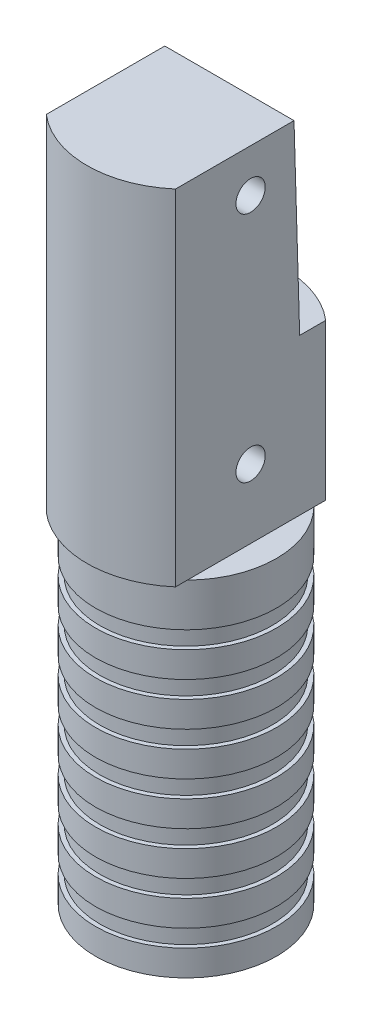
SolidWorks part; units mm, degrees
material "6061-T6 (SS)"
ref_plane "Front Plane" through (0, 0, 0) normal (0, 0, 1) x (1, 0, 0)
ref_plane "Top Plane" through (0, 0, 0) normal (0, 1, 0) x (1, 0, 0)
ref_plane "Right Plane" through (0, 0, 0) normal (1, 0, 0) x (0, 0, -1)
sketch "Sketch2" plane through (0, 0, 0) normal (0, 0, 1) x (1, 0, 0)
  line L0 (-10.5, 0) -> (10.5, 0)
  line L1 (10.5, 0) -> (10.5, -40)
  line L2 (10.5, -40) -> (-1, -40)
  line L4 (0, 0) -> (0, -40)
  line L6 (-10.5, -40) -> (-1, -40)
  line L7 (-10.5, 0) -> (-10.5, -40)
  point P4 (0, 0)
  dimension "D1" = 21
  dimension "D4" = 40
revolve "Revolve1" add sketch "Sketch2" angle 360 about L4 region at (-5.25, -20, 0)
sketch "Sketch3" plane through (0, 0, 0) normal (0, 0, 1) x (1, 0, 0)
  line L0 (-10.5, -40) -> (10.5, -40) construction
  line L1 (-10.5, -40) -> (10.5, -40)
  line L2 (10.5, -40) -> (10.5, -37)
  line L3 (10.5, -40) -> (10.5, 0) construction
  line L4 (10.5, -37) -> (10, -37)
  line L5 (10, -37) -> (10, -35)
  line L6 (10, -35) -> (10.5, -35)
  line L7 (10.5, -37) -> (10.5, -35)
  dimension "D1" = 2
  dimension "D2" = 0.5
  dimension "D3" = 3
revolve "Cut-Revolve1" cut sketch "Sketch3" angle 360 about L4
pattern_linear "LPattern1" count 7 spacing 5 along (0, 1, 0) of "Cut-Revolve1"
sketch "Sketch4" plane through (0, -40, 0) normal (0, -1, 0) x (1, 0, 0)
  point P0 (0, 0)
sketch "Sketch6" plane through (0, 0, 0) normal (0, 1, 0) x (1, 0, 0)
  line L0 (-7.5, 8.7178) -> (-7.5, -8.7178)
  line L2 (0, 0) -> (0, 11.5) construction
  line L3 (7.5, 8.7178) -> (7.5, -8.7178)
  line L4 (0, 0) -> (-7.5, 0) construction
  line L5 (-7.5, 1.5) -> (0, 1.5) construction
  arc A0 (7.5, 8.7178) -> (-7.5, 8.7178) centre (0, 0) ccw
  circle A1 centre (0, 0) radius 10.5 construction
  arc A2 (7.5, -8.7178) -> (-7.5, -8.7178) centre (0, 0) cw
  point P7 (-10.5, 0)
  dimension "D3" = 11.5
  dimension "D1" = 3
  dimension "D2" = 1.5
extrude "Boss-Extrude1" add sketch "Sketch6" along normal blind 40
hole_wizard "Ø15.0 (15) Diameter Hole1" positions "Sketch4" profile "Sketch5" hole size "Ø15.0" standard "ANSI Metric"
sketch "Sketch5" plane through (0, -40, 0) normal (1, 0, 0) x (0, 0, -1)
  line L0 (0, 0) -> (0, 34.5065)
  line L1 (0, 34.5065) -> (7.5, 30)
  line L2 (7.5, 30) -> (7.5, 0)
  line L5 (7.5, 0) -> (0, 0)
  line L10 (0, 34.5065) -> (-7.5, 30) construction
  line L11 (0, -6.35) -> (0, 107.95) construction
  dimension "Hole Dia." = 15
  dimension "Hole Depth" = 30
  dimension "Drill Angle" = 118
sketch "Sketch8" plane through (7.5, 0, 0) normal (1, 0, 0) x (0, 0, -1)
  line L2 (0, 8) -> (0, 35) construction
  line L3 (7.3485, 0) -> (-7.3485, 0) construction
  circle A0 centre (0, 8) radius 1.5 construction
  point P0 (0, 8)
  point P1 (0, 35)
  dimension "D1" = 3
  dimension "D2" = 8
  dimension "D3" = 27
hole_wizard "M3 Clearance Hole1" positions "Sketch8" profile "Sketch14" hole size "M3" standard "ANSI Metric" end condition through all
sketch "Sketch14" plane through (7.5, 8, 0) normal (0, 1, 0) x (0, 0, -1)
  line L0 (0, 0) -> (0, 18)
  line L1 (0, 18) -> (1.7, 18)
  line L2 (1.7, 18) -> (1.7, 0)
  line L5 (1.7, 0) -> (0, 0)
  line L11 (0, -6.35) -> (0, 107.95) construction
  dimension "Thru Hole Dia." = 3.4
  dimension "Thru Hole Depth" = 18
sketch "Sketch16" plane through (0, 0, 0) normal (1, 0, 0) x (0, 0, -1)
  line L0 (50.0175, 86.3497) -> (50.0175, 73.3497) construction
  line L1 (50.0175, -3.6503) -> (50.0175, 9.3497) construction
  line L2 (5.0377, 40) -> (5.6954, 18.0816)
  line L3 (5.6954, 18.0816) -> (11.5, 18.0816)
  line L4 (11.5, 40) -> (8.7178, 40) construction
  line L5 (11.5, 40) -> (8.7178, 40)
  line L6 (8.7178, 40) -> (5.0377, 40)
  line L8 (11.5, 18.0816) -> (11.5, 40)
  circle A0 centre (0, 8) radius 1.7 construction
  circle A1 centre (0, 35) radius 1.7 construction
  circle A2 centre (0, 8) radius 1.7
  circle A3 centre (0, 35) radius 1.7
  arc A4 (50.0175, -3.6503) -> (50.0175, 86.3497) centre (50.0175, 41.3497) cw construction
  arc A5 (50.0175, 73.3497) -> (50.0175, 9.3497) centre (50.0175, 41.3497) ccw construction
  dimension "D1" = 32
  dimension "D4" = 13
  dimension "D2" = 60.1162
  dimension "D3" = 50.4189
extrude "Cut-Extrude1" cut sketch "Sketch16" against normal through all both and the other way through all
